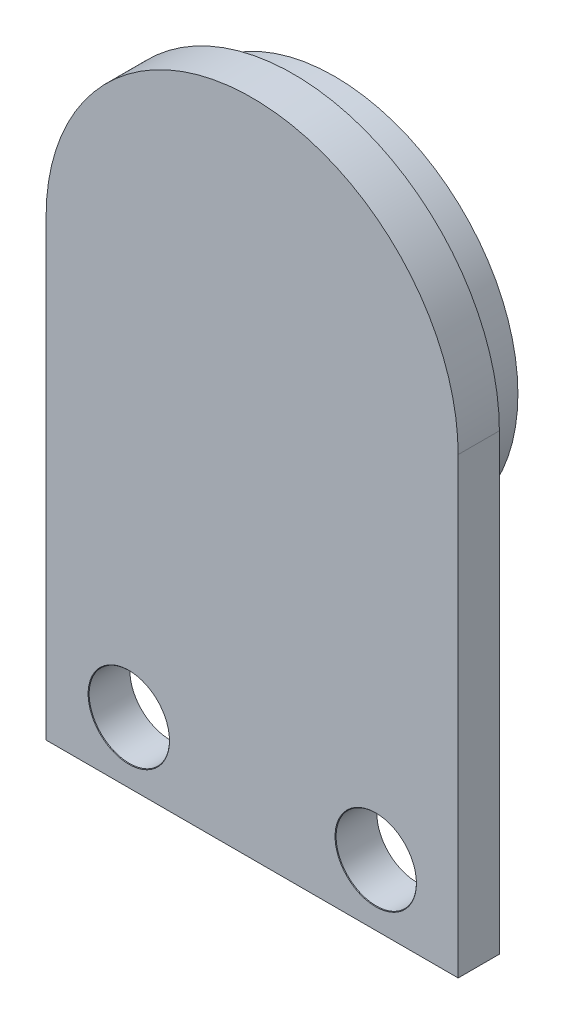
SolidWorks part; units mm, degrees
ref_plane "Front Plane" through (0, 0, 0) normal (0, 0, 1) x (1, 0, 0)
ref_plane "Top Plane" through (0, 0, 0) normal (0, 1, 0) x (1, 0, 0)
ref_plane "Right Plane" through (0, 0, 0) normal (1, 0, 0) x (0, 0, -1)
sketch "Sketch1" plane through (0, 0, 0) normal (0, 0, 1) x (1, 0, 0)
  line L0 (-10, 0) -> (-10, -22)
  line L1 (-10, -22) -> (10, -22)
  line L2 (10, -22) -> (10, 0)
  arc A0 (10, 0) -> (-10, 0) centre (0, 0) ccw
  dimension "D1" = 22
  dimension "D2" = 20
extrude "Boss-Extrude1" add sketch "Sketch1" along normal blind 2
sketch "Sketch2" plane through (0, 0, 0) normal (0, 0, -1) x (-1, 0, 0)
  circle A0 centre (0, 0) radius 8.9
  dimension "D1" = 17.8
extrude "Boss-Extrude2" add sketch "Sketch2" along normal blind 2
sketch "Sketch3" plane through (0, 0, -2) normal (0, 0, -1) x (-1, 0, 0)
  circle A0 centre (0, 0) radius 2
  dimension "D1" = 4
extrude "Boss-Extrude3" add sketch "Sketch3" along normal blind 3
hole_wizard "M3.5 Clearance Hole1" positions "Sketch4" profile "Sketch5" hole size "M3.5" standard "ANSI Metric" end condition through all
sketch "Sketch4" plane through (0, 0, 2) normal (0, 0, 1) x (1, 0, 0)
  point P2 (6, -19.0341)
  point P12 (-5.9848, -19.0341)
sketch "Sketch5" plane through (6, -19.0341, 2) normal (1, 0, 0) x (0, -1, 0)
  line L0 (0, 0) -> (0, 7)
  line L1 (0, 7) -> (1.95, 7)
  line L2 (1.95, 7) -> (1.95, 0.025)
  line L3 (1.95, 0.025) -> (1.975, 0)
  line L5 (1.975, 0) -> (0, 0)
  line L6 (-1.95, 0.025) -> (-1.975, 0) construction
  line L11 (0, -6.35) -> (0, 107.95) construction
  dimension "Thru Hole Dia." = 3.9
  dimension "Thru Hole Depth" = 7
  dimension "Near C'Sink Dia." = 3.95
  dimension "Near C'Sink Angle" = 90
